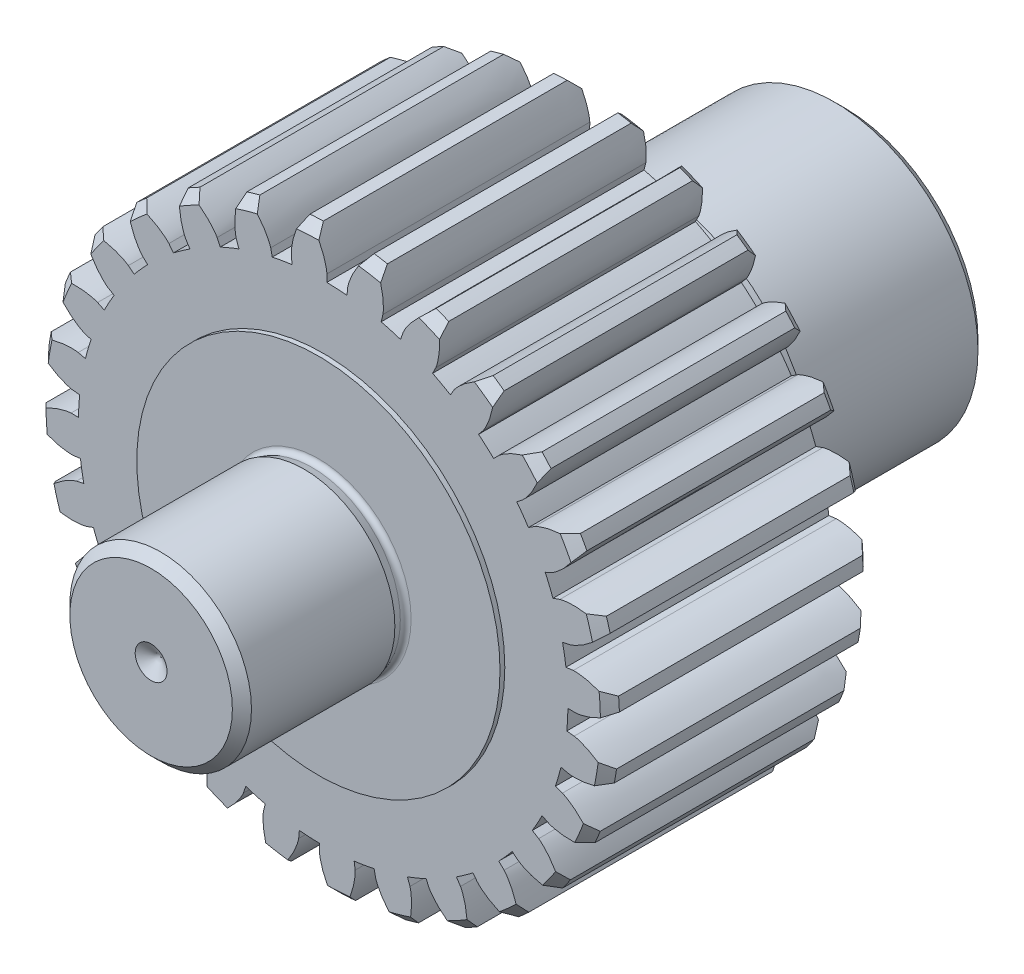
SolidWorks part; units mm, degrees
material "EN39B"
ref_plane "Front Plane" through (0, 0, 0) normal (0, 0, 1) x (1, 0, 0)
ref_plane "Top Plane" through (0, 0, 0) normal (0, 1, 0) x (1, 0, 0)
ref_plane "Right Plane" through (0, 0, 0) normal (1, 0, 0) x (0, 0, -1)
sketch "Sketch1" plane through (0, 0, 0) normal (1, 0, 0) x (0, 0, -1)
  line L0 (0, 0) -> (72.5, 0) construction
  line L1 (1, 0) -> (0, 1.6643)
  line L2 (0, 1.6643) -> (0, 8.5)
  line L3 (0, 8.5) -> (1, 9.5)
  line L4 (1, 9.5) -> (16, 9.5)
  line L5 (16, 9.5) -> (16.8451, 9.2246)
  line L6 (53.5, 15) -> (52.1181, 14.6641)
  line L7 (17.5, 9.7) -> (17.5, 19)
  line L8 (17.5, 19) -> (18, 19)
  line L9 (18, 19) -> (18, 29)
  line L10 (18, 29) -> (19, 30)
  line L11 (19, 30) -> (44.5, 30)
  line L12 (44.5, 30) -> (45.5, 29)
  line L13 (45.5, 29) -> (45.5, 18)
  line L14 (45.5, 18) -> (51.5, 18)
  line L15 (51.5, 18) -> (51.5, 15.15)
  line L18 (53.5, 15) -> (71.5, 15)
  line L19 (71.5, 15) -> (72.5, 14)
  line L20 (72.5, 14) -> (72.5, 9.1774)
  line L21 (72.5, 9.1774) -> (71.5, 8.6)
  line L22 (71.5, 8.6) -> (67.5, 8.6)
  line L23 (67.5, 8.6) -> (66.5762, 7)
  line L24 (66.5762, 7) -> (50.9238, 7)
  line L25 (50.9238, 7) -> (50, 8.6)
  line L26 (50, 8.6) -> (46, 8.6)
  line L27 (46, 8.6) -> (40.8326, 0)
  line L28 (40.8326, 0) -> (1, 0)
  arc A0 (16.8451, 9.2246) -> (17.5, 9.7) centre (17, 9.7) ccw
  arc A1 (51.5, 15.15) -> (52.1181, 14.6641) centre (52, 15.15) ccw
  dimension "D16" = 9.5
  dimension "D22" = 0.5
  dimension "D1" = 72.5
  dimension "D2" = 59
  dimension "D3" = 1
  dimension "D4" = 45
  dimension "D5" = 45
  dimension "D6" = 1
  dimension "D7" = 1
  dimension "D8" = 45
  dimension "D9" = 1
  dimension "D10" = 45
  dimension "D11" = 1
  dimension "D12" = 30
  dimension "D13" = 30
  dimension "D14" = 30
  dimension "D15" = 59
  dimension "D17" = 16
  dimension "D18" = 9.2
  dimension "D19" = 17.5
  dimension "D20" = 18
  dimension "D21" = 19
  dimension "D23" = 30
  dimension "D24" = 27.5
  dimension "D25" = 18
  dimension "D26" = 15
  dimension "D27" = 21
  dimension "D28" = 19
  dimension "D29" = 14.65
  dimension "D30" = 8.6
  dimension "D31" = 5
  dimension "D32" = 1
  dimension "D33" = 26.5
  dimension "D34" = 4
  dimension "D35" = 7
revolve "Revolve1" add sketch "Sketch1" angle 360 about L0
sketch "Sketch2" plane through (0, 0, 0) normal (0, 0, 1) x (1, 0, 0)
  line L0 (0, 0) -> (0, 28) construction
  line L1 (-25.5692, 28) -> (24.7138, 28) construction
  line L2 (0, 28) -> (22.9105, 36.3387) construction
  line L3 (0, 28) -> (-32.2296, 16.2694) construction
  line L4 (0, 0) -> (-8.999, 24.7246) construction
  line L5 (0, 0) -> (-7.1725, 25.3149) construction
  line L6 (0, 0) -> (-5.3077, 25.7705) construction
  line L7 (0, 0) -> (-3.4147, 26.0889) construction
  line L8 (0, 0) -> (-1.5036, 26.2684) construction
  line L9 (0, 0) -> (0.4156, 26.3081) construction
  line L10 (-7.1725, 25.3149) -> (0.1941, 27.4021) construction
  line L11 (-5.3077, 25.7705) -> (0.3109, 26.9277) construction
  line L12 (-3.4147, 26.0889) -> (0.3695, 26.5842) construction
  line L13 (-1.5036, 26.2684) -> (0.3899, 26.3768) construction
  line L14 (0, 0) -> (-10.7777, 24.0027) construction
  line L15 (0, 0) -> (-12.499, 23.1531) construction
  line L16 (0, 0) -> (-14.1537, 22.1802) construction
  line L17 (0, 0) -> (-15.7332, 21.0892) construction
  line L18 (0, 0) -> (-17.2289, 19.8861) construction
  line L19 (-10.7777, 24.0027) -> (-0.3113, 28.7024) construction
  line L20 (-12.499, 23.1531) -> (-0.7135, 29.5154) construction
  line L21 (-14.1537, 22.1802) -> (-1.245, 30.4176) construction
  line L22 (-15.7332, 21.0892) -> (-1.9204, 31.394) construction
  line L23 (-17.2289, 19.8861) -> (-2.753, 32.4277) construction
  circle A0 centre (0, 0) radius 28
  circle A1 centre (0, 0) radius 26.3114
  point P11 (-7.1948, 25.3813)
  point P16 (-5.3906, 26.038)
  point P17 (-3.5864, 26.6947)
  point P18 (-1.7822, 27.3513)
  point P28 (-17.9981, 21.4492)
  point P29 (-16.1938, 22.1059)
  point P30 (-14.3896, 22.7626)
  point P31 (-12.5854, 23.4193)
  point P32 (-10.7812, 24.076)
  dimension "D1" = 56
  dimension "D2" = 20
  dimension "D3" = 9.5766
  dimension "D4" = 1.92
  dimension "D5" = 1.92
  dimension "D6" = 1.92
  dimension "D7" = 1.92
  dimension "D8" = 1.8966
  dimension "D9" = 1.92
  dimension "D10" = 1.92
  dimension "D11" = 1.92
  dimension "D12" = 1.92
  dimension "D13" = 1.92
  dimension "D14" = 7.6566
  dimension "D15" = 5.7366
  dimension "D16" = 3.8166
  dimension "D17" = 7.6566
  dimension "D18" = 5.7366
  dimension "D19" = 3.8166
  dimension "D20" = 1.8966
  dimension "D21" = 9.5766
  dimension "D22" = 1.92
  dimension "D23" = 1.92
  dimension "D24" = 1.92
  dimension "D25" = 1.92
  dimension "D26" = 1.8966
  dimension "D27" = 1.92
  dimension "D28" = 1.92
  dimension "D29" = 1.92
  dimension "D30" = 1.92
  dimension "D31" = 1.92
  dimension "D32" = 11.4731
  dimension "D33" = 13.3931
  dimension "D34" = 15.3131
  dimension "D35" = 17.2331
  dimension "D36" = 19.1531
  dimension "D37" = 11.4731
  dimension "D38" = 13.3931
  dimension "D39" = 15.3131
  dimension "D40" = 17.2331
  dimension "D41" = 19.1531
sketch "Sketch3" plane through (0, 0, 0) normal (0, 0, 1) x (1, 0, 0)
  line L0 (0.3899, 26.3768) -> (0.3784, 25.5972)
  line L1 (0, 0) -> (-1.5692, 27.956) construction
  line L2 (-3.3392, 26.1675) -> (-3.2405, 25.3941)
  line L3 (6.2495, 25.6287) -> (6.0648, 24.8712)
  line L4 (2.5673, 26.2544) -> (2.4915, 25.4785)
  line L5 (11.7957, 23.5955) -> (11.4471, 22.8981)
  line L6 (8.3451, 25.0249) -> (8.0985, 24.2853)
  line L7 (16.7505, 20.3791) -> (16.2554, 19.7768)
  line L8 (13.7045, 22.5405) -> (13.2994, 21.8743)
  line L9 (20.8653, 16.1408) -> (20.2486, 15.6638)
  line L10 (18.3766, 18.9258) -> (17.8335, 18.3665)
  line L11 (23.9338, 11.0932) -> (23.2264, 10.7653)
  line L12 (22.1272, 14.3621) -> (21.4733, 13.9377)
  line L13 (25.8022, 5.4893) -> (25.0396, 5.327)
  line L14 (24.7683, 9.0783) -> (24.0363, 8.81)
  line L15 (26.3768, -0.3899) -> (25.5972, -0.3784)
  line L16 (26.1675, 3.3392) -> (25.3941, 3.2405)
  line L17 (25.6287, -6.2495) -> (24.8712, -6.0648)
  line L18 (26.2544, -2.5673) -> (25.4785, -2.4915)
  line L19 (23.5955, -11.7957) -> (22.8981, -11.4471)
  line L20 (25.0249, -8.3451) -> (24.2853, -8.0985)
  line L21 (20.3791, -16.7505) -> (19.7768, -16.2554)
  line L22 (22.5405, -13.7045) -> (21.8743, -13.2994)
  line L23 (16.1408, -20.8653) -> (15.6638, -20.2486)
  line L24 (18.9258, -18.3766) -> (18.3665, -17.8335)
  line L25 (11.0932, -23.9338) -> (10.7653, -23.2264)
  line L26 (14.3621, -22.1272) -> (13.9377, -21.4733)
  line L27 (5.4893, -25.8022) -> (5.327, -25.0396)
  line L28 (9.0783, -24.7683) -> (8.81, -24.0363)
  line L29 (-0.3899, -26.3768) -> (-0.3784, -25.5972)
  line L30 (3.3392, -26.1675) -> (3.2405, -25.3941)
  line L31 (-6.2495, -25.6287) -> (-6.0648, -24.8712)
  line L32 (-2.5673, -26.2544) -> (-2.4915, -25.4785)
  line L33 (-11.7957, -23.5955) -> (-11.4471, -22.8981)
  line L34 (-8.3451, -25.0249) -> (-8.0985, -24.2853)
  line L35 (-16.7505, -20.3791) -> (-16.2554, -19.7768)
  line L36 (-13.7045, -22.5405) -> (-13.2994, -21.8743)
  line L37 (-20.8653, -16.1408) -> (-20.2486, -15.6638)
  line L38 (-18.3766, -18.9258) -> (-17.8335, -18.3665)
  line L39 (-23.9338, -11.0932) -> (-23.2264, -10.7653)
  line L40 (-22.1272, -14.3621) -> (-21.4733, -13.9377)
  line L41 (-25.8022, -5.4893) -> (-25.0396, -5.327)
  line L42 (-24.7683, -9.0783) -> (-24.0363, -8.81)
  line L43 (-26.3768, 0.3899) -> (-25.5972, 0.3784)
  line L44 (-26.1675, -3.3392) -> (-25.3941, -3.2405)
  line L45 (-25.6287, 6.2495) -> (-24.8712, 6.0648)
  line L46 (-26.2544, 2.5673) -> (-25.4785, 2.4915)
  line L47 (-23.5955, 11.7957) -> (-22.8981, 11.4471)
  line L48 (-25.0249, 8.3451) -> (-24.2853, 8.0985)
  line L49 (-20.3791, 16.7505) -> (-19.7768, 16.2554)
  line L50 (-22.5405, 13.7045) -> (-21.8743, 13.2994)
  line L51 (-16.1408, 20.8653) -> (-15.6638, 20.2486)
  line L52 (-18.9258, 18.3766) -> (-18.3665, 17.8335)
  line L53 (-11.0932, 23.9338) -> (-10.7653, 23.2264)
  line L54 (-14.3621, 22.1272) -> (-13.9377, 21.4733)
  line L55 (-5.4893, 25.8022) -> (-5.327, 25.0396)
  line L56 (-9.0783, 24.7683) -> (-8.81, 24.0363)
  circle A0 centre (0, 0) radius 30
  circle A1 centre (0, 0) radius 25.6
  circle A2 centre (0, 0) radius 28 construction
  spline S0 degree 3 poles (-0.9773, 29.9841) (-0.8859, 29.8298) (-0.6489, 29.4103) (-0.3307, 28.7446) (-0.0019, 28.0493) (0.1866, 27.4484) (0.3232, 26.9071) (0.3777, 26.5621) (0.3899, 26.3768) knots 0.437527 0.437527 0.437527 0.437527 0.515359 0.646608 0.757769 0.848729 0.919421 1 1 1 1
  spline S1 degree 3 poles (-2.3843, 29.9051) (-2.4579, 29.7415) (-2.6464, 29.2982) (-2.8881, 28.6011) (-3.1371, 27.8733) (-3.2571, 27.2551) (-3.3323, 26.702) (-3.3478, 26.353) (-3.3392, 26.1675) knots 0.437527 0.437527 0.437527 0.437527 0.515359 0.646608 0.757769 0.848729 0.919421 1 1 1 1
  spline S2 degree 3 poles (4.33, 29.6859) (4.2219, 29.5428) (3.9394, 29.1525) (3.5486, 28.5267) (3.144, 27.8725) (2.8893, 27.2965) (2.693, 26.774) (2.6002, 26.4372) (2.5673, 26.2544) knots 0.437527 0.437527 0.437527 0.437527 0.515359 0.646608 0.757769 0.848729 0.919421 1 1 1 1
  spline S3 degree 3 poles (5.7193, 29.4498) (5.7741, 29.279) (5.9118, 28.8173) (6.0739, 28.0975) (6.2397, 27.3464) (6.2898, 26.7186) (6.3025, 26.1606) (6.2788, 25.8121) (6.2495, 25.6287) knots 0.437527 0.437527 0.437527 0.437527 0.515359 0.646608 0.757769 0.848729 0.919421 1 1 1 1
  spline S4 degree 3 poles (10.8272, 27.9781) (10.6899, 27.8626) (10.3277, 27.545) (9.8074, 27.0218) (9.2673, 26.4741) (8.8909, 25.9692) (8.5833, 25.5035) (8.4179, 25.1958) (8.3451, 25.0249) knots 0.437527 0.437527 0.437527 0.437527 0.515359 0.646608 0.757769 0.848729 0.919421 1 1 1 1
  spline S5 degree 3 poles (12.1291, 27.4388) (12.1445, 27.2601) (12.176, 26.7793) (12.1739, 26.0415) (12.1685, 25.2723) (12.0775, 24.6491) (11.9658, 24.1023) (11.8651, 23.7678) (11.7957, 23.5955) knots 0.437527 0.437527 0.437527 0.437527 0.515359 0.646608 0.757769 0.848729 0.919421 1 1 1 1
  spline S6 degree 3 poles (16.7814, 24.8673) (16.6219, 24.7853) (16.1981, 24.5562) (15.5745, 24.1619) (14.926, 23.7482) (14.4467, 23.3397) (14.0431, 22.9541) (13.8134, 22.6909) (13.7045, 22.5405) knots 0.437527 0.437527 0.437527 0.437527 0.515359 0.646608 0.757769 0.848729 0.919421 1 1 1 1
  spline S7 degree 3 poles (17.9307, 24.0519) (17.9059, 23.8742) (17.8297, 23.3985) (17.6634, 22.6796) (17.487, 21.931) (17.2597, 21.3436) (17.029, 20.8353) (16.8565, 20.5316) (16.7505, 20.3791) knots 0.437527 0.437527 0.437527 0.437527 0.515359 0.646608 0.757769 0.848729 0.919421 1 1 1 1
  spline S8 degree 3 poles (21.8942, 20.5096) (21.7204, 20.4652) (21.2562, 20.3361) (20.5605, 20.0905) (19.8363, 19.8314) (19.2781, 19.5398) (18.7988, 19.2537) (18.5163, 19.0483) (18.3766, 18.9258) knots 0.437527 0.437527 0.437527 0.437527 0.515359 0.646608 0.757769 0.848729 0.919421 1 1 1 1
  spline S9 degree 3 poles (22.8331, 19.4589) (22.7695, 19.2912) (22.5893, 18.8444) (22.2673, 18.1805) (21.9287, 17.4899) (21.5763, 16.9679) (21.2384, 16.5236) (21.0026, 16.2659) (20.8653, 16.1408) knots 0.437527 0.437527 0.437527 0.437527 0.515359 0.646608 0.757769 0.848729 0.919421 1 1 1 1
  spline S10 degree 3 poles (25.9091, 15.1235) (25.7298, 15.1188) (25.2485, 15.0963) (24.5156, 15.0117) (23.7518, 14.9202) (23.1427, 14.7601) (22.6118, 14.5878) (22.2907, 14.4504) (22.1272, 14.3621) knots 0.437527 0.437527 0.437527 0.437527 0.515359 0.646608 0.757769 0.848729 0.919421 1 1 1 1
  spline S11 degree 3 poles (26.5907, 13.8901) (26.4913, 13.7408) (26.2162, 13.3453) (25.7545, 12.7698) (25.2707, 12.1718) (24.8111, 11.7413) (24.3827, 11.3834) (24.0955, 11.1846) (23.9338, 11.0932) knots 0.437527 0.437527 0.437527 0.437527 0.515359 0.646608 0.757769 0.848729 0.919421 1 1 1 1
  spline S12 degree 3 poles (28.6248, 8.979) (28.4489, 9.0143) (27.9747, 9.0995) (27.2413, 9.1801) (26.4764, 9.2608) (25.8469, 9.2403) (25.291, 9.1905) (24.9473, 9.128) (24.7683, 9.0783) knots 0.437527 0.437527 0.437527 0.437527 0.515359 0.646608 0.757769 0.848729 0.919421 1 1 1 1
  spline S13 degree 3 poles (29.0148, 7.6249) (28.8847, 7.5014) (28.5285, 7.1771) (27.9503, 6.7187) (27.3456, 6.2434) (26.8017, 5.9259) (26.3044, 5.6723) (25.9802, 5.5424) (25.8022, 5.4893) knots 0.437527 0.437527 0.437527 0.437527 0.515359 0.646608 0.757769 0.848729 0.919421 1 1 1 1
  spline S14 degree 3 poles (29.9051, 2.3843) (29.7415, 2.4579) (29.2982, 2.6464) (28.6011, 2.8881) (27.8733, 3.1371) (27.2551, 3.2571) (26.702, 3.3323) (26.353, 3.3478) (26.1675, 3.3392) knots 0.437527 0.437527 0.437527 0.437527 0.515359 0.646608 0.757769 0.848729 0.919421 1 1 1 1
  spline S15 degree 3 poles (29.9841, 0.9773) (29.8298, 0.8859) (29.4103, 0.6489) (28.7446, 0.3307) (28.0493, 0.0019) (27.4484, -0.1866) (26.9071, -0.3232) (26.5621, -0.3777) (26.3768, -0.3899) knots 0.437527 0.437527 0.437527 0.437527 0.515359 0.646608 0.757769 0.848729 0.919421 1 1 1 1
  spline S16 degree 3 poles (29.6859, -4.33) (29.5428, -4.2219) (29.1525, -3.9394) (28.5267, -3.5486) (27.8725, -3.144) (27.2965, -2.8893) (26.774, -2.693) (26.4372, -2.6002) (26.2544, -2.5673) knots 0.437527 0.437527 0.437527 0.437527 0.515359 0.646608 0.757769 0.848729 0.919421 1 1 1 1
  spline S17 degree 3 poles (29.4498, -5.7193) (29.279, -5.7741) (28.8173, -5.9118) (28.0975, -6.0739) (27.3464, -6.2397) (26.7186, -6.2898) (26.1606, -6.3025) (25.8121, -6.2788) (25.6287, -6.2495) knots 0.437527 0.437527 0.437527 0.437527 0.515359 0.646608 0.757769 0.848729 0.919421 1 1 1 1
  spline S18 degree 3 poles (27.9781, -10.8272) (27.8626, -10.6899) (27.545, -10.3277) (27.0218, -9.8074) (26.4741, -9.2673) (25.9692, -8.8909) (25.5035, -8.5833) (25.1958, -8.4179) (25.0249, -8.3451) knots 0.437527 0.437527 0.437527 0.437527 0.515359 0.646608 0.757769 0.848729 0.919421 1 1 1 1
  spline S19 degree 3 poles (27.4388, -12.1291) (27.2601, -12.1445) (26.7793, -12.176) (26.0415, -12.1739) (25.2723, -12.1685) (24.6491, -12.0775) (24.1023, -11.9658) (23.7678, -11.8651) (23.5955, -11.7957) knots 0.437527 0.437527 0.437527 0.437527 0.515359 0.646608 0.757769 0.848729 0.919421 1 1 1 1
  spline S20 degree 3 poles (24.8673, -16.7814) (24.7853, -16.6219) (24.5562, -16.1981) (24.1619, -15.5745) (23.7482, -14.926) (23.3397, -14.4467) (22.9541, -14.0431) (22.6909, -13.8134) (22.5405, -13.7045) knots 0.437527 0.437527 0.437527 0.437527 0.515359 0.646608 0.757769 0.848729 0.919421 1 1 1 1
  spline S21 degree 3 poles (24.0519, -17.9307) (23.8742, -17.9059) (23.3985, -17.8297) (22.6796, -17.6634) (21.931, -17.487) (21.3436, -17.2597) (20.8353, -17.029) (20.5316, -16.8565) (20.3791, -16.7505) knots 0.437527 0.437527 0.437527 0.437527 0.515359 0.646608 0.757769 0.848729 0.919421 1 1 1 1
  spline S22 degree 3 poles (20.5096, -21.8942) (20.4652, -21.7204) (20.3361, -21.2562) (20.0905, -20.5605) (19.8314, -19.8363) (19.5398, -19.2781) (19.2537, -18.7988) (19.0483, -18.5163) (18.9258, -18.3766) knots 0.437527 0.437527 0.437527 0.437527 0.515359 0.646608 0.757769 0.848729 0.919421 1 1 1 1
  spline S23 degree 3 poles (19.4589, -22.8331) (19.2912, -22.7695) (18.8444, -22.5893) (18.1805, -22.2673) (17.4899, -21.9287) (16.9679, -21.5763) (16.5236, -21.2384) (16.2659, -21.0026) (16.1408, -20.8653) knots 0.437527 0.437527 0.437527 0.437527 0.515359 0.646608 0.757769 0.848729 0.919421 1 1 1 1
  spline S24 degree 3 poles (15.1235, -25.9091) (15.1188, -25.7298) (15.0963, -25.2485) (15.0117, -24.5156) (14.9202, -23.7518) (14.7601, -23.1427) (14.5878, -22.6118) (14.4504, -22.2907) (14.3621, -22.1272) knots 0.437527 0.437527 0.437527 0.437527 0.515359 0.646608 0.757769 0.848729 0.919421 1 1 1 1
  spline S25 degree 3 poles (13.8901, -26.5907) (13.7408, -26.4913) (13.3453, -26.2162) (12.7698, -25.7545) (12.1718, -25.2707) (11.7413, -24.8111) (11.3834, -24.3827) (11.1846, -24.0955) (11.0932, -23.9338) knots 0.437527 0.437527 0.437527 0.437527 0.515359 0.646608 0.757769 0.848729 0.919421 1 1 1 1
  spline S26 degree 3 poles (8.979, -28.6248) (9.0143, -28.4489) (9.0995, -27.9747) (9.1801, -27.2413) (9.2608, -26.4764) (9.2403, -25.8469) (9.1905, -25.291) (9.128, -24.9473) (9.0783, -24.7683) knots 0.437527 0.437527 0.437527 0.437527 0.515359 0.646608 0.757769 0.848729 0.919421 1 1 1 1
  spline S27 degree 3 poles (7.6249, -29.0148) (7.5014, -28.8847) (7.1771, -28.5285) (6.7187, -27.9503) (6.2434, -27.3456) (5.9259, -26.8017) (5.6723, -26.3044) (5.5424, -25.9802) (5.4893, -25.8022) knots 0.437527 0.437527 0.437527 0.437527 0.515359 0.646608 0.757769 0.848729 0.919421 1 1 1 1
  spline S28 degree 3 poles (2.3843, -29.9051) (2.4579, -29.7415) (2.6464, -29.2982) (2.8881, -28.6011) (3.1371, -27.8733) (3.2571, -27.2551) (3.3323, -26.702) (3.3478, -26.353) (3.3392, -26.1675) knots 0.437527 0.437527 0.437527 0.437527 0.515359 0.646608 0.757769 0.848729 0.919421 1 1 1 1
  spline S29 degree 3 poles (0.9773, -29.9841) (0.8859, -29.8298) (0.6489, -29.4103) (0.3307, -28.7446) (0.0019, -28.0493) (-0.1866, -27.4484) (-0.3232, -26.9071) (-0.3777, -26.5621) (-0.3899, -26.3768) knots 0.437527 0.437527 0.437527 0.437527 0.515359 0.646608 0.757769 0.848729 0.919421 1 1 1 1
  spline S30 degree 3 poles (-4.33, -29.6859) (-4.2219, -29.5428) (-3.9394, -29.1525) (-3.5486, -28.5267) (-3.144, -27.8725) (-2.8893, -27.2965) (-2.693, -26.774) (-2.6002, -26.4372) (-2.5673, -26.2544) knots 0.437527 0.437527 0.437527 0.437527 0.515359 0.646608 0.757769 0.848729 0.919421 1 1 1 1
  spline S31 degree 3 poles (-5.7193, -29.4498) (-5.7741, -29.279) (-5.9118, -28.8173) (-6.0739, -28.0975) (-6.2397, -27.3464) (-6.2898, -26.7186) (-6.3025, -26.1606) (-6.2788, -25.8121) (-6.2495, -25.6287) knots 0.437527 0.437527 0.437527 0.437527 0.515359 0.646608 0.757769 0.848729 0.919421 1 1 1 1
  spline S32 degree 3 poles (-10.8272, -27.9781) (-10.6899, -27.8626) (-10.3277, -27.545) (-9.8074, -27.0218) (-9.2673, -26.4741) (-8.8909, -25.9692) (-8.5833, -25.5035) (-8.4179, -25.1958) (-8.3451, -25.0249) knots 0.437527 0.437527 0.437527 0.437527 0.515359 0.646608 0.757769 0.848729 0.919421 1 1 1 1
  spline S33 degree 3 poles (-12.1291, -27.4388) (-12.1445, -27.2601) (-12.176, -26.7793) (-12.1739, -26.0415) (-12.1685, -25.2723) (-12.0775, -24.6491) (-11.9658, -24.1023) (-11.8651, -23.7678) (-11.7957, -23.5955) knots 0.437527 0.437527 0.437527 0.437527 0.515359 0.646608 0.757769 0.848729 0.919421 1 1 1 1
  spline S34 degree 3 poles (-16.7814, -24.8673) (-16.6219, -24.7853) (-16.1981, -24.5562) (-15.5745, -24.1619) (-14.926, -23.7482) (-14.4467, -23.3397) (-14.0431, -22.9541) (-13.8134, -22.6909) (-13.7045, -22.5405) knots 0.437527 0.437527 0.437527 0.437527 0.515359 0.646608 0.757769 0.848729 0.919421 1 1 1 1
  spline S35 degree 3 poles (-17.9307, -24.0519) (-17.9059, -23.8742) (-17.8297, -23.3985) (-17.6634, -22.6796) (-17.487, -21.931) (-17.2597, -21.3436) (-17.029, -20.8353) (-16.8565, -20.5316) (-16.7505, -20.3791) knots 0.437527 0.437527 0.437527 0.437527 0.515359 0.646608 0.757769 0.848729 0.919421 1 1 1 1
  spline S36 degree 3 poles (-21.8942, -20.5096) (-21.7204, -20.4652) (-21.2562, -20.3361) (-20.5605, -20.0905) (-19.8363, -19.8314) (-19.2781, -19.5398) (-18.7988, -19.2537) (-18.5163, -19.0483) (-18.3766, -18.9258) knots 0.437527 0.437527 0.437527 0.437527 0.515359 0.646608 0.757769 0.848729 0.919421 1 1 1 1
  spline S37 degree 3 poles (-22.8331, -19.4589) (-22.7695, -19.2912) (-22.5893, -18.8444) (-22.2673, -18.1805) (-21.9287, -17.4899) (-21.5763, -16.9679) (-21.2384, -16.5236) (-21.0026, -16.2659) (-20.8653, -16.1408) knots 0.437527 0.437527 0.437527 0.437527 0.515359 0.646608 0.757769 0.848729 0.919421 1 1 1 1
  spline S38 degree 3 poles (-25.9091, -15.1235) (-25.7298, -15.1188) (-25.2485, -15.0963) (-24.5156, -15.0117) (-23.7518, -14.9202) (-23.1427, -14.7601) (-22.6118, -14.5878) (-22.2907, -14.4504) (-22.1272, -14.3621) knots 0.437527 0.437527 0.437527 0.437527 0.515359 0.646608 0.757769 0.848729 0.919421 1 1 1 1
  spline S39 degree 3 poles (-26.5907, -13.8901) (-26.4913, -13.7408) (-26.2162, -13.3453) (-25.7545, -12.7698) (-25.2707, -12.1718) (-24.8111, -11.7413) (-24.3827, -11.3834) (-24.0955, -11.1846) (-23.9338, -11.0932) knots 0.437527 0.437527 0.437527 0.437527 0.515359 0.646608 0.757769 0.848729 0.919421 1 1 1 1
  spline S40 degree 3 poles (-28.6248, -8.979) (-28.4489, -9.0143) (-27.9747, -9.0995) (-27.2413, -9.1801) (-26.4764, -9.2608) (-25.8469, -9.2403) (-25.291, -9.1905) (-24.9473, -9.128) (-24.7683, -9.0783) knots 0.437527 0.437527 0.437527 0.437527 0.515359 0.646608 0.757769 0.848729 0.919421 1 1 1 1
  spline S41 degree 3 poles (-29.0148, -7.6249) (-28.8847, -7.5014) (-28.5285, -7.1771) (-27.9503, -6.7187) (-27.3456, -6.2434) (-26.8017, -5.9259) (-26.3044, -5.6723) (-25.9802, -5.5424) (-25.8022, -5.4893) knots 0.437527 0.437527 0.437527 0.437527 0.515359 0.646608 0.757769 0.848729 0.919421 1 1 1 1
  spline S42 degree 3 poles (-29.9051, -2.3843) (-29.7415, -2.4579) (-29.2982, -2.6464) (-28.6011, -2.8881) (-27.8733, -3.1371) (-27.2551, -3.2571) (-26.702, -3.3323) (-26.353, -3.3478) (-26.1675, -3.3392) knots 0.437527 0.437527 0.437527 0.437527 0.515359 0.646608 0.757769 0.848729 0.919421 1 1 1 1
  spline S43 degree 3 poles (-29.9841, -0.9773) (-29.8298, -0.8859) (-29.4103, -0.6489) (-28.7446, -0.3307) (-28.0493, -0.0019) (-27.4484, 0.1866) (-26.9071, 0.3232) (-26.5621, 0.3777) (-26.3768, 0.3899) knots 0.437527 0.437527 0.437527 0.437527 0.515359 0.646608 0.757769 0.848729 0.919421 1 1 1 1
  spline S44 degree 3 poles (-29.6859, 4.33) (-29.5428, 4.2219) (-29.1525, 3.9394) (-28.5267, 3.5486) (-27.8725, 3.144) (-27.2965, 2.8893) (-26.774, 2.693) (-26.4372, 2.6002) (-26.2544, 2.5673) knots 0.437527 0.437527 0.437527 0.437527 0.515359 0.646608 0.757769 0.848729 0.919421 1 1 1 1
  spline S45 degree 3 poles (-29.4498, 5.7193) (-29.279, 5.7741) (-28.8173, 5.9118) (-28.0975, 6.0739) (-27.3464, 6.2397) (-26.7186, 6.2898) (-26.1606, 6.3025) (-25.8121, 6.2788) (-25.6287, 6.2495) knots 0.437527 0.437527 0.437527 0.437527 0.515359 0.646608 0.757769 0.848729 0.919421 1 1 1 1
  spline S46 degree 3 poles (-27.9781, 10.8272) (-27.8626, 10.6899) (-27.545, 10.3277) (-27.0218, 9.8074) (-26.4741, 9.2673) (-25.9692, 8.8909) (-25.5035, 8.5833) (-25.1958, 8.4179) (-25.0249, 8.3451) knots 0.437527 0.437527 0.437527 0.437527 0.515359 0.646608 0.757769 0.848729 0.919421 1 1 1 1
  spline S47 degree 3 poles (-27.4388, 12.1291) (-27.2601, 12.1445) (-26.7793, 12.176) (-26.0415, 12.1739) (-25.2723, 12.1685) (-24.6491, 12.0775) (-24.1023, 11.9658) (-23.7678, 11.8651) (-23.5955, 11.7957) knots 0.437527 0.437527 0.437527 0.437527 0.515359 0.646608 0.757769 0.848729 0.919421 1 1 1 1
  spline S48 degree 3 poles (-24.8673, 16.7814) (-24.7853, 16.6219) (-24.5562, 16.1981) (-24.1619, 15.5745) (-23.7482, 14.926) (-23.3397, 14.4467) (-22.9541, 14.0431) (-22.6909, 13.8134) (-22.5405, 13.7045) knots 0.437527 0.437527 0.437527 0.437527 0.515359 0.646608 0.757769 0.848729 0.919421 1 1 1 1
  spline S49 degree 3 poles (-24.0519, 17.9307) (-23.8742, 17.9059) (-23.3985, 17.8297) (-22.6796, 17.6634) (-21.931, 17.487) (-21.3436, 17.2597) (-20.8353, 17.029) (-20.5316, 16.8565) (-20.3791, 16.7505) knots 0.437527 0.437527 0.437527 0.437527 0.515359 0.646608 0.757769 0.848729 0.919421 1 1 1 1
  spline S50 degree 3 poles (-20.5096, 21.8942) (-20.4652, 21.7204) (-20.3361, 21.2562) (-20.0905, 20.5605) (-19.8314, 19.8363) (-19.5398, 19.2781) (-19.2537, 18.7988) (-19.0483, 18.5163) (-18.9258, 18.3766) knots 0.437527 0.437527 0.437527 0.437527 0.515359 0.646608 0.757769 0.848729 0.919421 1 1 1 1
  spline S51 degree 3 poles (-19.4589, 22.8331) (-19.2912, 22.7695) (-18.8444, 22.5893) (-18.1805, 22.2673) (-17.4899, 21.9287) (-16.9679, 21.5763) (-16.5236, 21.2384) (-16.2659, 21.0026) (-16.1408, 20.8653) knots 0.437527 0.437527 0.437527 0.437527 0.515359 0.646608 0.757769 0.848729 0.919421 1 1 1 1
  spline S52 degree 3 poles (-15.1235, 25.9091) (-15.1188, 25.7298) (-15.0963, 25.2485) (-15.0117, 24.5156) (-14.9202, 23.7518) (-14.7601, 23.1427) (-14.5878, 22.6118) (-14.4504, 22.2907) (-14.3621, 22.1272) knots 0.437527 0.437527 0.437527 0.437527 0.515359 0.646608 0.757769 0.848729 0.919421 1 1 1 1
  spline S53 degree 3 poles (-13.8901, 26.5907) (-13.7408, 26.4913) (-13.3453, 26.2162) (-12.7698, 25.7545) (-12.1718, 25.2707) (-11.7413, 24.8111) (-11.3834, 24.3827) (-11.1846, 24.0955) (-11.0932, 23.9338) knots 0.437527 0.437527 0.437527 0.437527 0.515359 0.646608 0.757769 0.848729 0.919421 1 1 1 1
  spline S54 degree 3 poles (-8.979, 28.6248) (-9.0143, 28.4489) (-9.0995, 27.9747) (-9.1801, 27.2413) (-9.2608, 26.4764) (-9.2403, 25.8469) (-9.1905, 25.291) (-9.128, 24.9473) (-9.0783, 24.7683) knots 0.437527 0.437527 0.437527 0.437527 0.515359 0.646608 0.757769 0.848729 0.919421 1 1 1 1
  spline S55 degree 3 poles (-7.6249, 29.0148) (-7.5014, 28.8847) (-7.1771, 28.5285) (-6.7187, 27.9503) (-6.2434, 27.3456) (-5.9259, 26.8017) (-5.6723, 26.3044) (-5.5424, 25.9802) (-5.4893, 25.8022) knots 0.437527 0.437527 0.437527 0.437527 0.515359 0.646608 0.757769 0.848729 0.919421 1 1 1 1
  point P523 (0, 0)
  dimension "D1" = 60
  dimension "D2" = 51.2
  dimension "D3" = 1.57
  dimension "D4" = 28
extrude "Cut-Extrude1" cut sketch "Sketch3" against normal blind 72.5 contours A0 S55 L55 A1 L2 S1 | S2 A0 S0 L0 A1 L4 | S4 A0 S3 L3 A1 L6 | S6 A0 S5 L5 A1 L8 | S8 A0 S7 L7 A1 L10 | S10 A0 S9 L9 A1 L12 | S12 A0 S11 L11 A1 L14 | S14 A0 S13 L13 A1 L16 | S16 A0 S15 L15 A1 L18 | S18 A0 S17 L17 A1 L20 | S20 A0 S19 L19 A1 L22 | S22 A0 S21 L21 A1 L24 | S24 A0 S23 L23 A1 L26 | S26 A0 S25 L25 A1 L28 | S28 A0 S27 L27 A1 L30 | S30 A0 S29 L29 A1 L32 | S32 A0 S31 L31 A1 L34 | S34 A0 S33 L33 A1 L36 | S36 A0 S35 L35 A1 L38 | S38 A0 S37 L37 A1 L40 | S40 A0 S39 L39 A1 L42 | S42 A0 S41 L41 A1 L44 | S44 A0 S43 L43 A1 L46 | S46 A0 S45 L45 A1 L48 | S48 A0 S47 L47 A1 L50 | S50 A0 S49 L49 A1 L52 | S52 A0 S51 L51 A1 L54 | S54 A0 S53 L53 A1 L56 region at (1.5797, 28.1145, 0) region at (-4.716, 27.7612, 0) region at (7.7961, 27.0581, 0) region at (-10.7752, 26.0157, 0) region at (13.6217, 24.6449, 0) region at (-16.2941, 22.9657, 0) region at (18.7642, 20.9959, 0) region at (-20.9959, 18.7642, 0) region at (22.9657, 16.2941, 0) region at (-24.6449, 13.6217, 0) region at (26.0157, 10.7752, 0) region at (-27.0581, 7.7961, 0) region at (27.7612, 4.716, 0) region at (-28.1145, 1.5797, 0) region at (28.1145, -1.5797, 0) region at (-27.7612, -4.716, 0) region at (27.0581, -7.7961, 0) region at (-26.0157, -10.7752, 0) region at (24.6449, -13.6217, 0) region at (-22.9657, -16.2941, 0) region at (20.9959, -18.7642, 0) region at (-18.7642, -20.9959, 0) region at (16.2941, -22.9657, 0) region at (-13.6217, -24.6449, 0) region at (10.7752, -26.0157, 0) region at (-7.7961, -27.0581, 0) region at (4.716, -27.7612, 0) region at (-1.5797, -28.1145, 0)
sketch "Sketch5" plane through (0, 0, -72.5) normal (0, 0, -1) x (-1, 0, 0)
  line L0 (0, 0) -> (0, 7.2) construction
  line L1 (0, 7.2) -> (6.4554, 10.927) construction
  line L2 (9.9223, 7.2) -> (-6.7612, 7.2) construction
  line L3 (0, 7.2) -> (-7.9492, 2.6105) construction
  line L4 (0, 0) -> (-3.1177, 5.4) construction
  line L5 (0, 0) -> (-2.4748, 5.7232) construction
  line L6 (0, 0) -> (-1.7989, 5.9703) construction
  line L7 (0, 0) -> (-1.0991, 6.1378) construction
  line L8 (0, 0) -> (-0.3846, 6.2235) construction
  line L9 (0, 0) -> (0.335, 6.2264) construction
  line L10 (-2.4748, 5.7232) -> (0.1687, 6.8663) construction
  line L11 (-1.7989, 5.9703) -> (0.2693, 6.5934) construction
  line L12 (-1.0991, 6.1378) -> (0.3184, 6.3916) construction
  line L13 (-0.3846, 6.2235) -> (0.334, 6.2679) construction
  line L14 (0, 0) -> (-3.7191, 5.0048) construction
  line L15 (0, 0) -> (-4.2709, 4.543) construction
  line L16 (0, 0) -> (-4.7659, 4.0207) construction
  line L17 (0, 0) -> (-5.1974, 3.4448) construction
  line L18 (0, 0) -> (-5.5597, 2.8231) construction
  line L19 (-3.7191, 5.0048) -> (-0.2516, 7.5815) construction
  line L20 (-4.2709, 4.543) -> (-0.5989, 7.9952) construction
  line L21 (-4.7659, 4.0207) -> (-1.0518, 8.4233) construction
  line L22 (-5.1974, 3.4448) -> (-1.6175, 8.8461) construction
  line L23 (-5.5597, 2.8231) -> (-2.2999, 9.2429) construction
  circle A0 centre (0, 0) radius 7.2
  circle A1 centre (0, 0) radius 6.2354
  point P14 (-2.4942, 5.76)
  point P16 (-1.8706, 6.12)
  point P17 (-1.2471, 6.48)
  point P18 (-0.6235, 6.84)
  point P20 (-6.2354, 3.6)
  point P29 (-5.6118, 3.96)
  point P30 (-4.9883, 4.32)
  point P31 (-4.3648, 4.68)
  point P32 (-3.7412, 5.04)
  dimension "D1" = 14.4
  dimension "D2" = 30
  dimension "D3" = 3.6
  dimension "D4" = 0.72
  dimension "D5" = 0.72
  dimension "D6" = 0.72
  dimension "D7" = 0.72
  dimension "D8" = 0.72
  dimension "D9" = 1.44
  dimension "D10" = 2.16
  dimension "D11" = 2.88
  dimension "D12" = 0.72
  dimension "D13" = 0.72
  dimension "D14" = 0.72
  dimension "D15" = 0.72
  dimension "D16" = 0.72
  dimension "D17" = 2.88
  dimension "D18" = 2.16
  dimension "D19" = 1.44
  dimension "D20" = 0.72
  dimension "D21" = 3.6
  dimension "D22" = 0.72
  dimension "D23" = 0.72
  dimension "D24" = 0.72
  dimension "D25" = 0.72
  dimension "D26" = 0.72
  dimension "D27" = 0.72
  dimension "D28" = 0.72
  dimension "D29" = 0.72
  dimension "D30" = 0.72
  dimension "D31" = 0.72
  dimension "D32" = 4.32
  dimension "D33" = 5.04
  dimension "D34" = 5.76
  dimension "D35" = 6.48
  dimension "D36" = 7.2
  dimension "D37" = 4.32
  dimension "D38" = 5.04
  dimension "D39" = 5.76
  dimension "D40" = 6.48
  dimension "D41" = 7.2
sketch "Sketch6" plane through (0, 0, -72.5) normal (0, 0, -1) x (-1, 0, 0)
  line L0 (0, 0) -> (-1.2496, 7.0907) construction
  circle A0 centre (0, 0) radius 8.6
  circle A1 centre (0, 0) radius 7
  circle A2 centre (0, 0) radius 7.2 construction
  spline S0 degree 3 poles (-1.1696, 8.5201) (-1.1299, 8.4883) (-0.93, 8.3241) (-0.6098, 8.023) (-0.2606, 7.6094) (-0.0342, 7.2687) (0.0739, 7.0673) (0.1073, 6.9992) knots 0.326567 0.326567 0.326567 0.326567 0.363636 0.515151 0.646464 0.757575 0.812912 0.812912 0.812912 0.812912
  spline S1 degree 3 poles (-1.8135, 8.4066) (-1.8399, 8.3632) (-1.9717, 8.1406) (-2.1696, 7.7481) (-2.3564, 7.2401) (-2.4527, 6.8424) (-2.4854, 6.6163) (-2.4936, 6.5408) knots 0.326567 0.326567 0.326567 0.326567 0.363636 0.515151 0.646464 0.757575 0.812912 0.812912 0.812912 0.812912
  spline S2 degree 3 poles (4.0145, 7.6055) (3.9663, 7.5893) (3.7223, 7.5034) (3.3183, 7.33) (2.8487, 7.0609) (2.5193, 6.8182) (2.3489, 6.666) (2.2942, 6.6134) knots 0.326567 0.326567 0.326567 0.326567 0.363636 0.515151 0.646464 0.757575 0.812912 0.812912 0.812912 0.812912
  spline S3 degree 3 poles (4.5806, 7.2786) (4.5906, 7.2287) (4.6382, 6.9745) (4.69, 6.5379) (4.6916, 5.9967) (4.6461, 5.5901) (4.5994, 5.3664) (4.5812, 5.2927) knots 0.326567 0.326567 0.326567 0.326567 0.363636 0.515151 0.646464 0.757575 0.812912 0.812912 0.812912 0.812912
  spline S4 degree 3 poles (7.964, 3.2457) (7.9166, 3.2642) (7.6745, 3.3553) (7.2536, 3.4821) (6.7209, 3.5779) (6.3126, 3.6036) (6.0842, 3.5966) (6.0084, 3.5915) knots 0.326567 0.326567 0.326567 0.326567 0.363636 0.515151 0.646464 0.757575 0.812912 0.812912 0.812912 0.812912
  spline S5 degree 3 poles (8.1876, 2.6313) (8.1632, 2.5867) (8.0362, 2.3614) (7.7952, 1.9937) (7.4486, 1.578) (7.1523, 1.2958) (6.9728, 1.1545) (6.9115, 1.1097) knots 0.326567 0.326567 0.326567 0.326567 0.363636 0.515151 0.646464 0.757575 0.812912 0.812912 0.812912 0.812912
  spline S6 degree 3 poles (8.1871, -2.6328) (8.1627, -2.5882) (8.0358, -2.3628) (7.7949, -1.9951) (7.4483, -1.5793) (7.1521, -1.2971) (6.9726, -1.1557) (6.9113, -1.1109) knots 0.326567 0.326567 0.326567 0.326567 0.363636 0.515151 0.646464 0.757575 0.812912 0.812912 0.812912 0.812912
  spline S7 degree 3 poles (7.9634, -3.2471) (7.9161, -3.2656) (7.6739, -3.3567) (7.253, -3.4834) (6.7202, -3.5791) (6.3119, -3.6048) (6.0835, -3.5976) (6.0078, -3.5925) knots 0.326567 0.326567 0.326567 0.326567 0.363636 0.515151 0.646464 0.757575 0.812912 0.812912 0.812912 0.812912
  spline S8 degree 3 poles (4.5793, -7.2794) (4.5893, -7.2295) (4.637, -6.9753) (4.6888, -6.5388) (4.6906, -5.9975) (4.6451, -5.5909) (4.5984, -5.3672) (4.5803, -5.2935) knots 0.326567 0.326567 0.326567 0.326567 0.363636 0.515151 0.646464 0.757575 0.812912 0.812912 0.812912 0.812912
  spline S9 degree 3 poles (4.0131, -7.6062) (3.965, -7.59) (3.7209, -7.504) (3.317, -7.3306) (2.8474, -7.0614) (2.5181, -6.8186) (2.3477, -6.6664) (2.293, -6.6138) knots 0.326567 0.326567 0.326567 0.326567 0.363636 0.515151 0.646464 0.757575 0.812912 0.812912 0.812912 0.812912
  spline S10 degree 3 poles (-1.1711, -8.5199) (-1.1314, -8.4881) (-0.9315, -8.324) (-0.6112, -8.0229) (-0.2619, -7.6094) (-0.0354, -7.2687) (0.0726, -7.0673) (0.1061, -6.9992) knots 0.326567 0.326567 0.326567 0.326567 0.363636 0.515151 0.646464 0.757575 0.812912 0.812912 0.812912 0.812912
  spline S11 degree 3 poles (-1.815, -8.4063) (-1.8414, -8.3629) (-1.9731, -8.1402) (-2.171, -7.7477) (-2.3577, -7.2396) (-2.4539, -6.842) (-2.4866, -6.6158) (-2.4947, -6.5404) knots 0.326567 0.326567 0.326567 0.326567 0.363636 0.515151 0.646464 0.757575 0.812912 0.812912 0.812912 0.812912
  spline S12 degree 3 poles (-6.3736, -5.7738) (-6.3228, -5.775) (-6.0641, -5.7778) (-5.6252, -5.753) (-5.0919, -5.6608) (-4.6994, -5.5453) (-4.4872, -5.4606) (-4.4177, -5.4299) knots 0.326567 0.326567 0.326567 0.326567 0.363636 0.515151 0.646464 0.757575 0.812912 0.812912 0.812912 0.812912
  spline S13 degree 3 poles (-6.7938, -5.273) (-6.7862, -5.2227) (-6.7439, -4.9675) (-6.6432, -4.5396) (-6.4597, -4.0304) (-6.2778, -3.6639) (-6.1574, -3.4697) (-6.1151, -3.4066) knots 0.326567 0.326567 0.326567 0.326567 0.363636 0.515151 0.646464 0.757575 0.812912 0.812912 0.812912 0.812912
  spline S14 degree 3 poles (-8.5938, -0.3261) (-8.5556, -0.3597) (-8.3593, -0.5281) (-8.0072, -0.7912) (-7.5393, -1.0634) (-7.1644, -1.2273) (-6.9473, -1.2988) (-6.8744, -1.3199) knots 0.326567 0.326567 0.326567 0.326567 0.363636 0.515151 0.646464 0.757575 0.812912 0.812912 0.812912 0.812912
  spline S15 degree 3 poles (-8.5938, 0.3276) (-8.5556, 0.3612) (-8.3592, 0.5296) (-8.007, 0.7927) (-7.5391, 1.0648) (-7.1642, 1.2286) (-6.9471, 1.3) (-6.8742, 1.3211) knots 0.326567 0.326567 0.326567 0.326567 0.363636 0.515151 0.646464 0.757575 0.812912 0.812912 0.812912 0.812912
  spline S16 degree 3 poles (-6.7929, 5.2742) (-6.7852, 5.2239) (-6.743, 4.9687) (-6.6424, 4.5408) (-6.459, 4.0315) (-6.2771, 3.665) (-6.1568, 3.4708) (-6.1145, 3.4077) knots 0.326567 0.326567 0.326567 0.326567 0.363636 0.515151 0.646464 0.757575 0.812912 0.812912 0.812912 0.812912
  spline S17 degree 3 poles (-6.3726, 5.775) (-6.3218, 5.7761) (-6.0631, 5.7789) (-5.6242, 5.754) (-5.0909, 5.6617) (-4.6984, 5.5462) (-4.4862, 5.4614) (-4.4168, 5.4307) knots 0.326567 0.326567 0.326567 0.326567 0.363636 0.515151 0.646464 0.757575 0.812912 0.812912 0.812912 0.812912
  point P121 (0, 0)
  dimension "D1" = 17.2
  dimension "D2" = 14
  dimension "D3" = 1.256
extrude "Cut-Extrude2" cut sketch "Sketch6" against normal blind 25 contours S17 A0 S16 A1 | A0 S1 A1 S0 | S3 A0 S2 A1 | S5 A0 S4 A1 | S7 A0 S6 A1 | S9 A0 S8 A1 | S11 A0 S10 A1 | S13 A0 S12 A1 | S15 A0 S14 A1 region at (-7.1685, 2.6084, -72.5) region at (-7.168, -2.6097, -72.5) region at (-3.8147, 6.606, -72.5) region at (-3.8136, -6.6066, -72.5) region at (1.324, 7.5125, -72.5) region at (1.3253, -7.5123, -72.5) region at (5.8432, 4.9039, -72.5) region at (5.844, -4.9029, -72.5) region at (7.6283, 0.0007, -72.5)
